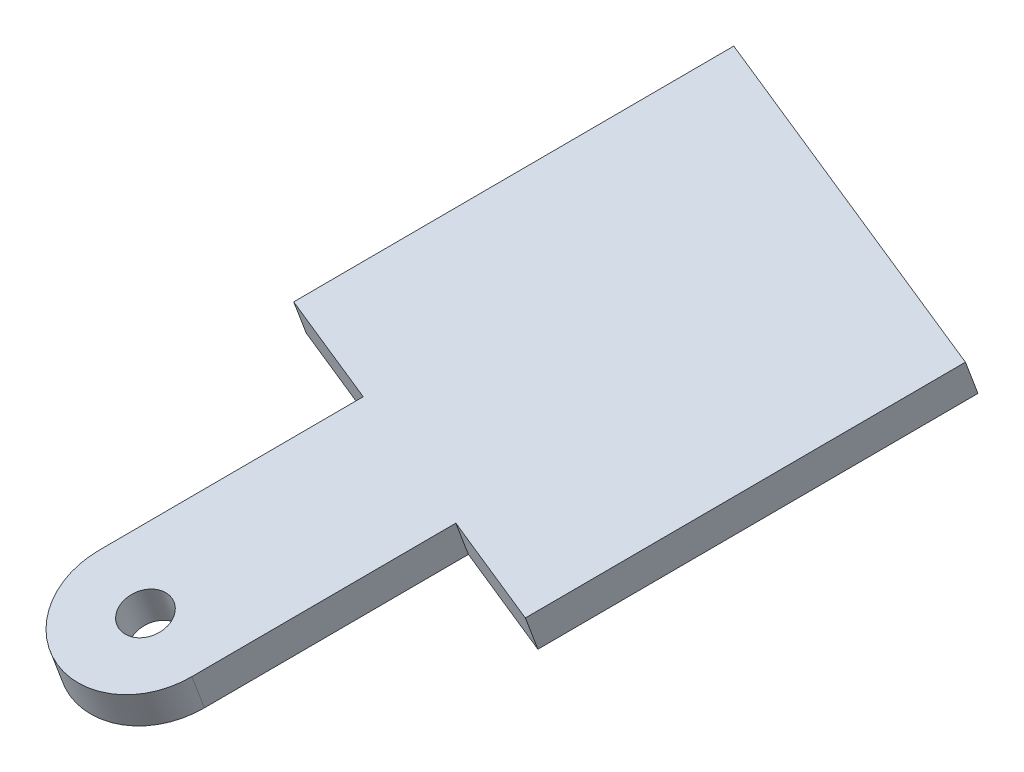
SolidWorks part; units mm, degrees
ref_plane "Front Plane" through (0, 0, 0) normal (0, 0, 1) x (1, 0, 0)
ref_plane "Top Plane" through (0, 0, 0) normal (0, 1, 0) x (1, 0, 0)
ref_plane "Right Plane" through (0, 0, 0) normal (1, 0, 0) x (0, 0, -1)
sketch "Sketch2" plane through (-485.0156, 24.0931, 406.7236) normal (0.0128, 0.933, 0.3598) x (-0.3313, -0.3355, 0.8818)
  line L0 (-234.1386, 173.8491) -> (-304.1386, 173.8491) construction
  line L1 (-234.1386, 163.8491) -> (-264.1386, 163.8491)
  line L2 (-234.1386, 183.8491) -> (-264.1386, 183.8491)
  line L3 (-314.1386, 148.8491) -> (-314.1386, 198.8491)
  line L4 (-314.1386, 198.8491) -> (-264.1386, 198.8491)
  line L5 (-264.1386, 198.8491) -> (-264.1386, 183.8491)
  line L6 (-264.1386, 148.8491) -> (-314.1386, 148.8491)
  line L7 (-264.1386, 163.8491) -> (-264.1386, 148.8491)
  arc A0 (-234.1386, 163.8491) -> (-234.1386, 183.8491) centre (-234.1386, 173.8491) ccw
  point P2 (-269.1386, 173.8491)
  point P11 (-314.1386, 173.8491)
  dimension "D1" = 20
  dimension "D2" = 80
  dimension "D3" = 50
  dimension "D4" = 50
extrude "Boss-Extrude1" add sketch "Sketch2" along normal blind 5
sketch "Sketch4" plane through (2.1435, 156.3652, 60.2987) normal (0.0128, 0.933, 0.3598) x (0.9999, -0.0088, -0.0128)
  circle A0 centre (-247.3324, -205.3534) radius 3
  dimension "D1" = 6
extrude "Cut-Extrude1" cut sketch "Sketch4" against normal blind 10
